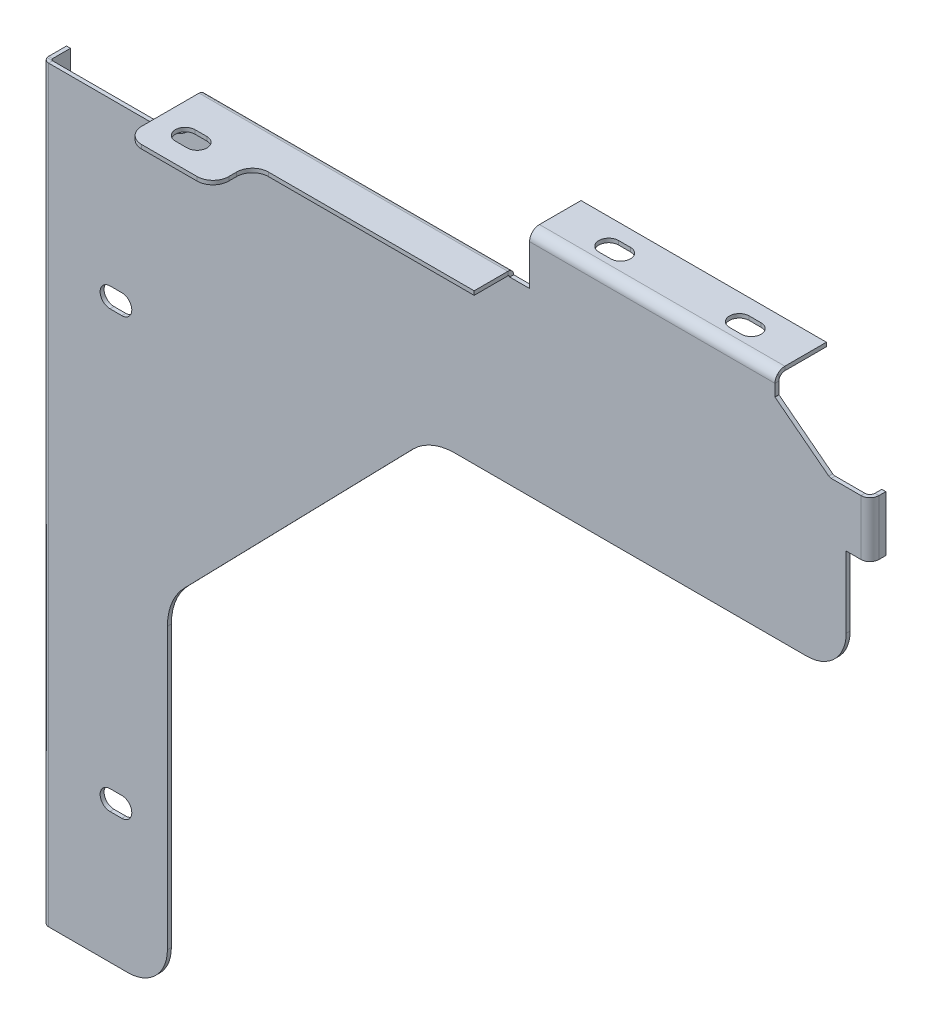
SolidWorks part; units mm, degrees
note: The reader was unsure of these and kept them because the rebuilt part matched: flange length of "Edge-Flange1", "Edge-Flange2", "Edge-Flange3", "Edge-Flange5".
ref_plane "Front Plane" through (0, 0, 0) normal (0, 0, 1) x (1, 0, 0)
ref_plane "Top Plane" through (0, 0, 0) normal (0, 1, 0) x (1, 0, 0)
ref_plane "Right Plane" through (0, 0, 0) normal (1, 0, 0) x (0, 0, -1)
sketch "Sketch1" plane through (0, 0, 0) normal (0, 0, 1) x (1, 0, 0)
  line L0 (0, 0) -> (0, -212.19)
  line L1 (0, -212.19) -> (20.5, -212.19)
  line L2 (30.5, -202.19) -> (30.5, -131.4032)
  line L4 (103.1812, -57.19) -> (192, -57.19)
  line L5 (202, -47.19) -> (202, 0)
  line L6 (202, 0) -> (0, 0)
  line L7 (34.8934, -120.7966) -> (92.5746, -61.5834)
  arc A0 (20.5, -212.19) -> (30.5, -202.19) centre (20.5, -202.19) ccw
  arc A1 (92.5746, -61.5834) -> (103.1812, -57.19) centre (103.1812, -72.19) cw
  arc A2 (30.5, -131.4032) -> (34.8934, -120.7966) centre (45.5, -131.4032) cw
  arc A3 (192, -57.19) -> (202, -47.19) centre (192, -47.19) ccw
  point P13 (30.5, -212.19)
  point P16 (96.968, -58.722)
  point P19 (30.5, -125.19)
  dimension "D4" = 10
  dimension "D7" = 15
  dimension "D9" = 10
  dimension "D1" = 30.5
  dimension "D2" = 87
  dimension "D3" = 155
  dimension "D5" = 94
  dimension "D6" = 57.19
  dimension "D8" = 202
base flange "Base-Flange1" sketch "Sketch1" thickness 1 reverse thickness direction no parameters "D1"=1.27
edge flange "Edge-Flange1" sketch "Sketch8" flange angle 90 flange length 6 flange position material outside bend radius 0.5 thickness 1 relief rectangular parameters "D6"=10
sketch "Sketch8" plane through (0, 0, 0) normal (-1, 0, 0) x (0, -1, 0)
  line L2 (23.19, 0) -> (23.19, 5)
  line L3 (23.19, 5) -> (212.19, 5)
  line L4 (212.19, 5) -> (212.19, 0)
  line L7 (0, 0) -> (212.19, 0) construction
  line L8 (23.19, 0) -> (212.19, 0)
  dimension "D1" = 189
bend "EdgeBend1" bend radius 0.5 bend angle 90 parameters "D5"=1
sketch "Sketch9" plane through (0, 0, 0) normal (0, 0, 1) x (1, 0, 0)
  line L0 (202, 0) -> (0, 0) construction
  line L1 (-1, -23.19) -> (29, -23.19)
  line L2 (-1, -23.19) -> (-1, 0)
  line L3 (-1, 0) -> (39, 0)
  line L4 (39, -13.19) -> (39, 0)
  arc A0 (29, -23.19) -> (39, -13.19) centre (29, -13.19) ccw
  point P9 (39, -23.19)
  dimension "D2" = 10
  dimension "D1" = 40
extrude "Cut-Extrude1" cut sketch "Sketch9" against normal blind 10
edge flange "Edge-Flange2" sketch "Sketch12" flange angle 90 flange length 13 flange position material outside bend radius 1.5 thickness 1 relief rectangular parameters "D6"=10
sketch "Sketch12" plane through (0, 0, 0) normal (0, 1, 0) x (-1, 0, 0)
  line L2 (-184, 0) -> (-184, 12)
  line L3 (-184, 12) -> (-122, 12)
  line L4 (-122, 12) -> (-122, 0)
  line L7 (-202, 0) -> (-39, 0) construction
  line L8 (-184, 0) -> (-122, 0)
  dimension "D1" = 18
  dimension "D2" = 62
bend "EdgeBend2" bend radius 1.5 bend angle 90 parameters "D5"=2
sketch "Sketch13" plane through (0, 0, 0) normal (0, 0, 1) x (1, 0, 0)
  line L0 (192, -57.19) -> (192, -29.19) construction
  line L1 (192, -29.19) -> (202, -29.19) construction
  line L2 (202, -47.19) -> (202, 0) construction
  line L3 (207, -29.19) -> (202, -29.19) construction
  line L4 (202, -29.19) -> (207, -29.19)
  line L5 (207, -29.19) -> (207, -15.19)
  line L6 (207, -15.19) -> (202, -15.19)
  line L7 (202, -15.19) -> (202, -29.19)
  dimension "D1" = 28
  dimension "D2" = 5
  dimension "D3" = 14
base flange "Tab1" sketch "Sketch13" thickness 1 reverse thickness direction no parameters "D1"=1.27
sketch "Sketch16" plane through (0, 0, 0) normal (0, 0, 1) x (1, 0, 0)
  line L0 (202, -15.19) -> (198.1877, -15.19)
  line L3 (184, 0) -> (202, 0)
  line L4 (202, -15.19) -> (202, 0) construction
  line L5 (202, 0) -> (184.5, 0) construction
  line L6 (202, 0) -> (202, -15.19)
  line L7 (184, 0) -> (184, -1.5)
  line L8 (184, -1.5) -> (184, -4.4754)
  line L10 (184.0194, -4.515) -> (197.5765, -14.9816)
  arc A1 (198.1877, -15.19) -> (197.5765, -14.9816) centre (198.1877, -14.19) cw
  arc A2 (184, -4.4754) -> (184.0194, -4.515) centre (184.05, -4.4754) ccw
  point P7 (199.4995, -10.8602)
  point P18 (184, -4.5)
  dimension "D2" = 1
  dimension "D4" = 0.05
  dimension "D1" = 5
  dimension "D3" = 3
extrude "Cut-Extrude4" cut sketch "Sketch16" against normal blind 10
edge flange "Edge-Flange3" sketch "Sketch19" flange angle 90 flange length 4 flange position material outside bend radius 1.27 thickness 1 relief rectangular parameters "D6"=10
sketch "Sketch19" plane through (207, 0, 0) normal (1, 0, 0) x (0, 1, 0)
  line L2 (-29.19, 0) -> (-29.19, 3)
  line L3 (-29.19, 3) -> (-15.19, 3)
  line L4 (-15.19, 3) -> (-15.19, 0)
  line L7 (-29.19, 0) -> (-15.19, 0) construction
  line L8 (-29.19, 0) -> (-15.19, 0)
bend "EdgeBend3" bend radius 1.27 bend angle 90 parameters "D5"=3
sketch "Sketch20" plane through (0, 0, 0) normal (0, 0, 1) x (1, 0, 0)
  line L0 (122, -0.75) -> (122, -11.75)
  line L1 (122, 0) -> (122, -1.5) construction
  line L2 (122, -11.75) -> (38.539, -11.75)
  line L3 (38.539, -11.75) -> (38.539, 0)
  line L4 (121.5, 0) -> (39, 0) construction
  line L5 (38.539, 0) -> (122, 0)
  line L6 (122, 0) -> (122, -0.75)
  dimension "D1" = 11
extrude "Cut-Extrude3" cut sketch "Sketch20" against normal blind 10
edge flange "Edge-Flange5" sketch "Sketch28" flange angle 90 flange length 10 flange position bend outside bend radius 0.5 thickness 1 relief rectangular parameters "D6"=10
sketch "Sketch28" plane through (0, -11.75, -1) normal (0, -1, 0) x (-1, 0, 0)
  line L2 (-117, 0) -> (-117, 9)
  line L3 (-117, 9) -> (-39, 9)
  line L4 (-39, 9) -> (-39, 0)
  line L9 (-39, 0) -> (-122, 0) construction
  line L10 (-39, 0) -> (-117, 0)
  dimension "D1" = 5
bend "EdgeBend5" bend radius 0.5 bend angle 90 parameters "D5"=4
sketch "Sketch33" plane through (0, -10.25, 0) normal (0, 1, 0) x (1, 0, 0)
  line L0 (39, 10) -> (61, 10)
  line L1 (39, 10) -> (117, 10) construction
  line L2 (61, 10) -> (61, 20)
  line L3 (61, 20) -> (39, 20)
  line L4 (39, 20) -> (39, 10)
  dimension "D1" = 22
  dimension "D2" = 10
base flange "Tab2" sketch "Sketch33" thickness 1 reverse thickness direction no parameters "D1"=1.27
fillet "Fillet1" radius 4 1 edges at (61, -10.75, -10)
fillet "Fillet2" radius 4 2 edges at (39, -10.75, -20) (61, -10.75, -20)
sketch "Sketch35" plane through (0, 1, 0) normal (0, 1, 0) x (1, 0, 0)
  line L0 (171.5, -5.5) -> (168.5, -5.5) construction
  line L1 (171.5, -8) -> (168.5, -8)
  line L2 (171.5, -3) -> (168.5, -3)
  line L3 (138.5, -5.5) -> (135.5, -5.5) construction
  line L4 (138.5, -8) -> (135.5, -8)
  line L5 (138.5, -3) -> (135.5, -3)
  line L6 (184, -12) -> (184, -1.5) construction
  line L7 (122, -12) -> (184, -12) construction
  line L8 (122, -1.5) -> (122, -12) construction
  arc A0 (171.5, -8) -> (171.5, -3) centre (171.5, -5.5) ccw
  arc A1 (168.5, -3) -> (168.5, -8) centre (168.5, -5.5) ccw
  arc A2 (138.5, -8) -> (138.5, -3) centre (138.5, -5.5) ccw
  arc A3 (135.5, -3) -> (135.5, -8) centre (135.5, -5.5) ccw
  point P2 (170, -5.5)
  point P8 (137, -5.5)
  point P14 (174, -5.5)
  point P19 (166, -5.5)
  point P20 (133, -5.5)
  dimension "D1" = 10
  dimension "D2" = 4
  dimension "D3" = 8
  dimension "D4" = 5
  dimension "D5" = 11
extrude "Cut-Extrude5" cut sketch "Sketch35" against normal blind 1 normal cut yes
sketch "Sketch36" plane through (0, -11.25, 0) normal (0, -1, 0) x (1, 0, 0)
  line L0 (49.5, -12.5) -> (46.5, -12.5) construction
  line L1 (49.5, -15) -> (46.5, -15)
  line L2 (49.5, -10) -> (46.5, -10)
  line L3 (57, -20) -> (43, -20) construction
  line L4 (39, -1.5) -> (39, -16) construction
  arc A0 (49.5, -15) -> (49.5, -10) centre (49.5, -12.5) ccw
  arc A1 (46.5, -10) -> (46.5, -15) centre (46.5, -12.5) ccw
  point P2 (48, -12.5)
  point P7 (44, -12.5)
  point P8 (52, -12.5)
  dimension "D1" = 5
  dimension "D2" = 8
  dimension "D3" = 5
  dimension "D4" = 5
extrude "Cut-Extrude6" cut sketch "Sketch36" against normal blind 1 normal cut yes
sketch "Sketch38" plane through (0, 0, 0) normal (0, 0, 1) x (1, 0, 0)
  line L0 (16, -176.69) -> (19, -176.69) construction
  line L1 (16, -174.19) -> (19, -174.19)
  line L2 (16, -179.19) -> (19, -179.19)
  line L3 (30.5, -202.19) -> (30.5, -131.4032) construction
  line L4 (0.5, -212.19) -> (20.5, -212.19) construction
  line L5 (16, -66.69) -> (19, -66.69) construction
  line L6 (16, -64.19) -> (19, -64.19)
  line L7 (16, -69.19) -> (19, -69.19)
  arc A0 (16, -174.19) -> (16, -179.19) centre (16, -176.69) ccw
  arc A1 (19, -179.19) -> (19, -174.19) centre (19, -176.69) ccw
  arc A2 (16, -64.19) -> (16, -69.19) centre (16, -66.69) ccw
  arc A3 (19, -69.19) -> (19, -64.19) centre (19, -66.69) ccw
  point P2 (17.5, -176.69)
  point P7 (21.5, -176.69)
  point P8 (13.5, -176.69)
  point P16 (17.5, -66.69)
  dimension "D1" = 5
  dimension "D2" = 8
  dimension "D3" = 9
  dimension "D4" = 33
  dimension "D6" = 105
  dimension "D5" = 2
extrude "Cut-Extrude7" cut sketch "Sketch38" against normal blind 1 normal cut yes
ref_plane "Plane1" through (0, 0, 12) normal (0, 0, 1) x (1, 0, 0)
mirror "Mirror1" about plane through (0, 0, 12) normal (0, 0, 1) of bodies 115
bend "DerivedBend1" bend radius 1.27 bend angle 90 parameters "D5"=1
bend "DerivedBend2" bend radius 0.5 bend angle 90 parameters "D5"=2
bend "DerivedBend3" bend radius 1.5 bend angle 90 parameters "D5"=3
bend "DerivedBend4" bend radius 0.5 bend angle 90 parameters "D5"=4
delete or keep bodies "Body-Delete/Keep 1" type delete bodies bodies 115
sketch "Bend-Lines1" [suppressed] plane through (0, 0, 0) normal (0, 1, 0) x (1, 0, 0)
sketch "Bounding-Box1" [suppressed] plane through (0, 0, 0) normal (0, 1, 0) x (1, 0, 0)
sheet metal parameters "Sheet-Metal1" thickness 1 parameters "D1"=1.27
flat pattern "Flat-Pattern1" [suppressed]
sketch "Bend-Lines2" plane through (0, 0, 0) normal (0, 1, 0) x (1, 0, 0)
sketch3d "Bounding-Box2" [suppressed]
  line L0 (20.5, -10, 0) -> (-181.5, -10, 0) construction
  line L1 (20.5, 192, 0) -> (-181.5, 192, 0) construction
  line L2 (20.5, -10, 0) -> (20.5, 192, 0) construction
  line L3 (-181.5, -10, 0) -> (-181.5, 192, 0) construction
sheet metal parameters "Sheet-Metal2" thickness 1 parameters "D1"=1.27
flat pattern "Flat-Pattern1"
sketch "Bend-Lines2" plane through (0, 0, 0) normal (0, 0, 1) x (1, 0, 0)
  line L0 (-0.0708, -13) -> (-0.0708, -202) construction
  line L1 (-0.0708, -13) -> (-0.0708, -202) construction
sketch3d "Bounding-Box2" [suppressed]
  line L0 (-25.6416, -10, 0) -> (181.5, -10, 0) construction
  line L1 (-25.6416, 192, 0) -> (181.5, 192, 0) construction
  line L2 (-25.6416, -10, 0) -> (-25.6416, 192, 0) construction
  line L3 (181.5, -10, 0) -> (181.5, 192, 0) construction
bend of the flat pattern "Flatten-<EdgeBend1>1"
sheet metal parameters "Sheet-Metal3" thickness 1 parameters "D1"=1.27
flat pattern "Flat-Pattern1"
sketch "Bend-Lines2" plane through (0, 0, 0) normal (0, 0, 1) x (1, 0, 0)
  line L0 (-0.0708, -13) -> (-0.0708, -202) construction
  line L1 (-0.0708, -13) -> (-0.0708, -202) construction
sketch3d "Bounding-Box2" [suppressed]
  line L0 (-25.6416, -10, 0) -> (181.5, -10, 0) construction
  line L1 (-25.6416, 192, 0) -> (181.5, 192, 0) construction
  line L2 (-25.6416, -10, 0) -> (-25.6416, 192, 0) construction
  line L3 (181.5, -10, 0) -> (181.5, 192, 0) construction
bend of the flat pattern "Flatten-<EdgeBend1>1"
sheet metal parameters "Sheet-Metal4" thickness 1 parameters "D1"=1.27
flat pattern "Flat-Pattern1" [suppressed]
sketch "Bend-Lines2" plane through (0, 0, 0) normal (0, 0, 1) x (1, 0, 0)
  line L0 (-0.0708, -13) -> (-0.0708, -202) construction
  line L1 (-0.0708, -13) -> (-0.0708, -202) construction
sketch3d "Bounding-Box2" [suppressed]
  line L0 (-25.6416, -10, 0) -> (181.5, -10, 0) construction
  line L1 (-25.6416, 192, 0) -> (181.5, 192, 0) construction
  line L2 (-25.6416, -10, 0) -> (-25.6416, 192, 0) construction
  line L3 (181.5, -10, 0) -> (181.5, 192, 0) construction
bend of the flat pattern "Flatten-<EdgeBend1>1"
bend of the flat pattern "Flatten-<EdgeBend2>1"
sheet metal parameters "Sheet-Metal5" thickness 1 parameters "D1"=1.27
flat pattern "Flat-Pattern5" [suppressed]
sketch "Bend-Lines3" plane through (0, 0, 0) normal (0, 1, 0) x (1, 0, 0)
sketch "Bounding-Box3" [suppressed] plane through (0, 0, 0) normal (0, 1, 0) x (1, 0, 0)
bend of the flat pattern "Flatten-<EdgeBend1>2"
bend of the flat pattern "Flatten-<EdgeBend2>2"
sheet metal parameters "Sheet-Metal7" thickness 1 parameters "D1"=1.27
flat pattern "Flat-Pattern5" [suppressed]
sketch "Bend-Lines3" plane through (0, 0, 0) normal (0, 1, 0) x (1, 0, 0)
sketch "Bounding-Box3" [suppressed] plane through (0, 0, 0) normal (0, 1, 0) x (1, 0, 0)
bend of the flat pattern "Flatten-<EdgeBend1>2"
bend of the flat pattern "Flatten-<EdgeBend3>1"
bend of the flat pattern "Flatten-<EdgeBend2>2"
sheet metal parameters "Sheet-Metal8" thickness 1 parameters "D1"=1.27
flat pattern "Flat-Pattern5" [suppressed]
sketch "Bend-Lines3" plane through (0, 0, 0) normal (0, 1, 0) x (1, 0, 0)
sketch "Bounding-Box3" [suppressed] plane through (0, 0, 0) normal (0, 1, 0) x (1, 0, 0)
bend of the flat pattern "Flatten-<EdgeBend1>2"
bend of the flat pattern "Flatten-<EdgeBend3>1"
bend of the flat pattern "Flatten-<EdgeBend2>2"
sheet metal parameters "Sheet-Metal10" thickness 1 parameters "D1"=1.27
flat pattern "Flat-Pattern5" [suppressed]
sketch "Bend-Lines3" plane through (0, 0, 0) normal (0, 1, 0) x (1, 0, 0)
sketch "Bounding-Box3" [suppressed] plane through (0, 0, 0) normal (0, 1, 0) x (1, 0, 0)
bend of the flat pattern "Flatten-<EdgeBend1>2"
bend of the flat pattern "Flatten-<EdgeBend3>1"
bend of the flat pattern "Flatten-<EdgeBend5>1"
bend of the flat pattern "Flatten-<EdgeBend2>2"
sheet metal parameters "Sheet-Metal11" thickness 1 parameters "D1"=1.27
flat pattern "Flat-Pattern11" [suppressed]
sketch "Bend-Lines4" plane through (0, 0, 0) normal (0, 1, 0) x (1, 0, 0)
sketch "Bounding-Box4" [suppressed] plane through (0, 0, 0) normal (0, 1, 0) x (1, 0, 0)
bend of the flat pattern "Flatten-<EdgeBend5>2"
bend of the flat pattern "Flatten-<EdgeBend3>2"
bend of the flat pattern "Flatten-<EdgeBend1>3"
bend of the flat pattern "Flatten-<EdgeBend2>3"
sheet metal parameters "Sheet-Metal12" thickness 1 parameters "D1"=1.27
flat pattern "Flat-Pattern5" [suppressed]
sketch "Bend-Lines3" plane through (0, 0, 0) normal (0, 1, 0) x (1, 0, 0)
sketch "Bounding-Box3" [suppressed] plane through (0, 0, 0) normal (0, 1, 0) x (1, 0, 0)
bend of the flat pattern "Flatten-<EdgeBend1>2"
bend of the flat pattern "Flatten-<EdgeBend2>2"
sheet metal parameters "Sheet-Metal13" thickness 1 parameters "D1"=1.27
flat pattern "Flat-Pattern11" [suppressed]
sketch "Bend-Lines4" plane through (0, 0, 0) normal (0, 1, 0) x (1, 0, 0)
sketch "Bounding-Box4" [suppressed] plane through (0, 0, 0) normal (0, 1, 0) x (1, 0, 0)
bend of the flat pattern "Flatten-<EdgeBend5>2"
bend of the flat pattern "Flatten-<EdgeBend3>2"
bend of the flat pattern "Flatten-<EdgeBend1>3"
bend of the flat pattern "Flatten-<EdgeBend2>3"
sheet metal parameters "Sheet-Metal14" thickness 1 parameters "D1"=1.27
flat pattern "Flat-Pattern11"
sketch "Bend-Lines4" plane through (0, 0, 0) normal (0, 1, 0) x (1, 0, 0)
sketch "Bounding-Box4" [suppressed] plane through (0, 0, 0) normal (0, 1, 0) x (1, 0, 0)
bend of the flat pattern "Flatten-<EdgeBend5>2"
bend of the flat pattern "Flatten-<EdgeBend3>2"
bend of the flat pattern "Flatten-<EdgeBend1>3"
bend of the flat pattern "Flatten-<EdgeBend2>3"
sheet metal parameters "Sheet-Metal15" thickness 1 parameters "D1"=1.27
flat pattern "Flat-Pattern11"
sketch "Bend-Lines4" plane through (0, 0, 0) normal (0, 1, 0) x (1, 0, 0)
sketch "Bounding-Box4" [suppressed] plane through (0, 0, 0) normal (0, 1, 0) x (1, 0, 0)
bend of the flat pattern "Flatten-<EdgeBend5>2"
bend of the flat pattern "Flatten-<EdgeBend3>2"
bend of the flat pattern "Flatten-<EdgeBend1>3"
bend of the flat pattern "Flatten-<EdgeBend2>3"
sheet metal parameters "Sheet-Metal16" thickness 1 parameters "D1"=1.27
flat pattern "Flat-Pattern16"
sketch "Bend-Lines5" plane through (0, 0, 0) normal (0, 1, 0) x (1, 0, 0)
sketch "Bounding-Box5" [suppressed] plane through (0, 0, 0) normal (0, 1, 0) x (1, 0, 0)
bend of the flat pattern "Flatten-<DerivedBend1>1"
bend of the flat pattern "Flatten-<DerivedBend2>1"
bend of the flat pattern "Flatten-<DerivedBend3>1"
bend of the flat pattern "Flatten-<DerivedBend4>1"
